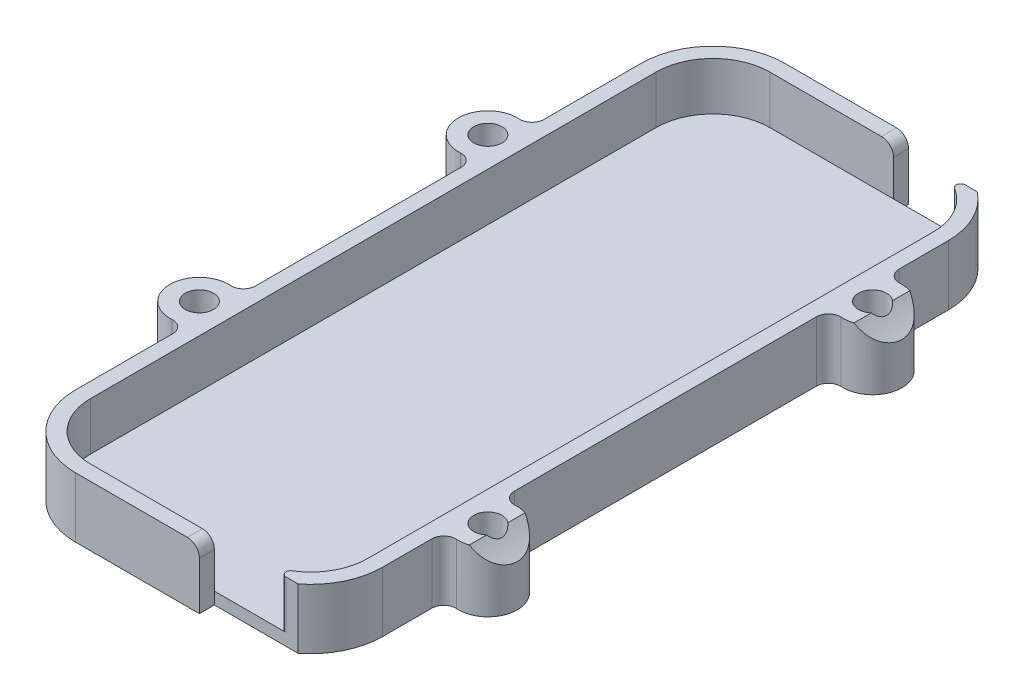
SolidWorks part; units mm, degrees
ref_plane "Front" through (0, 0, 0) normal (0, 0, 1) x (1, 0, 0)
ref_plane "Top" through (0, 0, 0) normal (0, 1, 0) x (1, 0, 0)
ref_plane "Right" through (0, 0, 0) normal (1, 0, 0) x (0, 0, -1)
ref_axis "side-side" through (80.9, 0, 0) along (-1, 0, 0)
ref_axis "up-down" through (0, 50, 0) along (0, -1, 0)
ref_axis "front-back" through (0, 0, -80.9) along (0, 0, 1)
sketch3d "3DSketch1"
  line L3 (-84.85, 48.65, 7.675) -> (-89, 48.65, 7.675)
  line L8 (-80.0996, 87.5542, 66.8971) -> (-111.9004, 87.5542, 66.8971)
  line L9 (-111.9004, 87.5542, 66.8971) -> (-111.9004, 87.5542, 49.7013)
  line L10 (-111.9004, 87.5542, 49.7013) -> (-80.0996, 87.5542, 49.7013)
  line L11 (-80.0996, 87.5542, 49.7013) -> (-80.0996, 87.5542, 66.8971)
  line L16 (-109.9954, 87.5542, 52) -> (-109.9954, 87.5542, 64.5984)
  line L17 (-109.9954, 87.5542, 64.5984) -> (-82.0046, 87.5542, 64.5984)
  line L18 (-82.0046, 87.5542, 64.5984) -> (-82.0046, 87.5542, 52)
  line L19 (-82.0046, 87.5542, 52) -> (-109.9954, 87.5542, 52)
  line L24 (-72, 34.65, 48) -> (-168, 34.65, 48)
  line L25 (-168, 34.65, 48) -> (-168, 62.65, 48)
  line L26 (-166, 64.65, 48) -> (-74, 64.65, 48)
  line L27 (-72, 62.65, 48) -> (-72, 34.65, 48)
  line L32 (-22.2, 34.65, -47.05) -> (-22.2, 34.65, 47.05)
  line L33 (-30.4, 34.65, 55.25) -> (-57.6, 34.65, 55.25)
  line L34 (-65.8, 34.65, 47.05) -> (-65.8, 34.65, -47.05)
  line L35 (-57.6, 34.65, -55.25) -> (-30.4, 34.65, -55.25)
  line L40 (-21.2, 35.65, 47.05) -> (-21.2, 35.65, -47.05)
  line L41 (-30.4, 35.65, -56.25) -> (-57.6, 35.65, -56.25)
  line L42 (-66.8, 35.65, -47.05) -> (-66.8, 35.65, 47.05)
  line L43 (-57.6, 35.65, 56.25) -> (-30.4, 35.65, 56.25)
  line L56 (-18.5394, 56.65, 57.65) -> (-36, 56.65, 57.65)
  line L57 (-36, 56.65, 57.65) -> (-36, 59.85, 57.65)
  line L58 (-34.5, 61.35, 57.65) -> (-24.4367, 61.35, 57.65)
  line L59 (26.2059, 54.95, 57.65) -> (34.5, 54.95, 57.65)
  line L60 (36, 53.45, 57.65) -> (36, 32.65, 57.65)
  line L61 (36, 32.65, 57.65) -> (-36, 32.65, 57.65)
  line L62 (-36, 32.65, 57.65) -> (-36, 53.65, 57.65)
  line L63 (-36, 53.65, 57.65) -> (-18.5394, 53.65, 57.65)
  line L64 (-96, 52.65, 40) -> (-96, 116.65, 40)
  line L65 (-96, 48.65, -44) -> (-96, 48.65, 36)
  line L66 (-96, 116.65, -48) -> (-96, 52.65, -48)
  line L67 (-96, 120.65, 36) -> (-96, 120.65, -44)
  line L80 (-24.4367, 61.35, -57.65) -> (-34.5, 61.35, -57.65)
  line L81 (-36, 59.85, -57.65) -> (-36, 56.65, -57.65)
  line L82 (-36, 56.65, -57.65) -> (-18.5394, 56.65, -57.65)
  line L83 (-18.5394, 53.65, -57.65) -> (-36, 53.65, -57.65)
  line L84 (-36, 53.65, -57.65) -> (-36, 32.65, -57.65)
  line L85 (-36, 32.65, -57.65) -> (36, 32.65, -57.65)
  line L86 (36, 32.65, -57.65) -> (36, 53.45, -57.65)
  line L87 (34.5, 54.95, -57.65) -> (26.2059, 54.95, -57.65)
  line L88 (-72, 34.65, -48) -> (-72, 62.65, -48)
  line L89 (-74, 64.65, -48) -> (-166, 64.65, -48)
  line L90 (-168, 62.65, -48) -> (-168, 34.65, -48)
  line L91 (-168, 34.65, -48) -> (-72, 34.65, -48)
  line L96 (-150, 32.65, -16) -> (38, 32.65, -16)
  line L97 (-152, 32.65, -78) -> (-152, 32.65, -18)
  line L98 (38, 32.65, -80) -> (-150, 32.65, -80)
  line L99 (40, 32.65, -18) -> (40, 32.65, -78)
  line L104 (-150, 32.65, 80) -> (38, 32.65, 80)
  line L105 (40, 32.65, 78) -> (40, 32.65, 18)
  line L106 (38, 32.65, 16) -> (-150, 32.65, 16)
  line L107 (-152, 32.65, 18) -> (-152, 32.65, 78)
  line L108 (-84.85, 48.65, 16.325) -> (-84.85, 48.65, 7.675)
  line L109 (-89, 48.65, 16.325) -> (-84.85, 48.65, 16.325)
  arc A4 (-168, 62.65, 48) -> (-166, 64.65, 48) centre (-166, 62.65, 48) ccw
  arc A5 (-74, 64.65, 48) -> (-72, 62.65, 48) centre (-74, 62.65, 48) ccw
  circle A6 centre (0, 55.15, 15.5) radius 17.6
  arc A12 (-22.2, 34.65, 47.05) -> (-30.4, 34.65, 55.25) centre (-30.4, 34.65, 47.05) ccw
  arc A13 (-57.6, 34.65, 55.25) -> (-65.8, 34.65, 47.05) centre (-57.6, 34.65, 47.05) ccw
  arc A14 (-65.8, 34.65, -47.05) -> (-57.6, 34.65, -55.25) centre (-57.6, 34.65, -47.05) ccw
  arc A15 (-30.4, 34.65, -55.25) -> (-22.2, 34.65, -47.05) centre (-30.4, 34.65, -47.05) ccw
  circle A16 centre (-96, 52.65, -44) radius 2.1
  arc A22 (-21.2, 35.65, -47.05) -> (-30.4, 35.65, -56.25) centre (-30.4, 35.65, -47.05) ccw
  arc A23 (-57.6, 35.65, -56.25) -> (-66.8, 35.65, -47.05) centre (-57.6, 35.65, -47.05) ccw
  arc A24 (-66.8, 35.65, 47.05) -> (-57.6, 35.65, 56.25) centre (-57.6, 35.65, 47.05) ccw
  arc A25 (-30.4, 35.65, 56.25) -> (-21.2, 35.65, 47.05) centre (-30.4, 35.65, 47.05) ccw
  circle A26 centre (-96, 84.65, -44) radius 2.1
  circle A28 centre (-96, 84.65, 36) radius 2.1
  arc A36 (-36, 59.85, 57.65) -> (-34.5, 61.35, 57.65) centre (-34.5, 59.85, 57.65) ccw
  arc A37 (-24.4367, 61.35, 57.65) -> (-20.7453, 63.8092, 57.65) centre (-24.4367, 65.35, 57.65) ccw
  arc A38 (-20.7453, 63.8092, 57.65) -> (22.2473, 58.376, 57.65) centre (0, 55.15, 57.65) ccw
  arc A39 (22.2473, 58.376, 57.65) -> (26.2059, 54.95, 57.65) centre (26.2059, 58.95, 57.65) ccw
  arc A40 (34.5, 54.95, 57.65) -> (36, 53.45, 57.65) centre (34.5, 53.45, 57.65) ccw
  arc A41 (-18.5394, 53.65, 57.65) -> (-18.5394, 56.65, 57.65) centre (0, 55.15, 57.65) ccw
  arc A46 (-96, 48.65, 36) -> (-96, 52.65, 40) centre (-96, 52.65, 36) ccw
  arc A47 (-96, 52.65, -48) -> (-96, 48.65, -44) centre (-96, 52.65, -44) ccw
  arc A48 (-96, 120.65, -44) -> (-96, 116.65, -48) centre (-96, 116.65, -44) ccw
  arc A49 (-96, 116.65, 40) -> (-96, 120.65, 36) centre (-96, 116.65, 36) ccw
  circle A50 centre (-96, 68.65, 36) radius 2.1
  circle A52 centre (-96, 52.65, 36) radius 2.1
  circle A54 centre (-96, 68.65, -44) radius 2.1
  arc A58 (-72, 62.65, -48) -> (-74, 64.65, -48) centre (-74, 62.65, -48) ccw
  arc A59 (-166, 64.65, -48) -> (-168, 62.65, -48) centre (-166, 62.65, -48) ccw
  arc A66 (26.2059, 54.95, -57.65) -> (22.2473, 58.376, -57.65) centre (26.2059, 58.95, -57.65) ccw
  arc A67 (22.2473, 58.376, -57.65) -> (-20.7453, 63.8092, -57.65) centre (0, 55.15, -57.65) ccw
  arc A68 (-20.7453, 63.8092, -57.65) -> (-24.4367, 61.35, -57.65) centre (-24.4367, 65.35, -57.65) ccw
  arc A69 (-34.5, 61.35, -57.65) -> (-36, 59.85, -57.65) centre (-34.5, 59.85, -57.65) ccw
  arc A70 (-18.5394, 56.65, -57.65) -> (-18.5394, 53.65, -57.65) centre (0, 55.15, -57.65) ccw
  arc A71 (36, 53.45, -57.65) -> (34.5, 54.95, -57.65) centre (34.5, 53.45, -57.65) ccw
  arc A78 (-152, 32.65, -18) -> (-150, 32.65, -16) centre (-150, 32.65, -18) ccw
  arc A79 (-150, 32.65, -80) -> (-152, 32.65, -78) centre (-150, 32.65, -78) ccw
  arc A80 (40, 32.65, -78) -> (38, 32.65, -80) centre (38, 32.65, -78) ccw
  arc A81 (38, 32.65, -16) -> (40, 32.65, -18) centre (38, 32.65, -18) ccw
  arc A86 (38, 32.65, 80) -> (40, 32.65, 78) centre (38, 32.65, 78) ccw
  arc A87 (40, 32.65, 18) -> (38, 32.65, 16) centre (38, 32.65, 18) ccw
  arc A88 (-150, 32.65, 16) -> (-152, 32.65, 18) centre (-150, 32.65, 18) ccw
  arc A89 (-152, 32.65, 78) -> (-150, 32.65, 80) centre (-150, 32.65, 78) ccw
  arc A119 (-130.34, 32.65, 28.19) -> (-130.34, 32.65, 24.49) centre (-130.34, 32.65, 26.34) ccw
  arc A120 (-130.34, 32.65, -35.81) -> (-130.34, 32.65, -39.51) centre (-130.34, 32.65, -37.66) ccw
  arc A121 (-136, 32.65, -38.15) -> (-136, 32.65, -41.85) centre (-136, 32.65, -40) ccw
  arc A122 (-72, 32.65, 25.85) -> (-72, 32.65, 22.15) centre (-72, 32.65, 24) ccw
  arc A123 (-80, 32.65, 33.85) -> (-80, 32.65, 30.15) centre (-80, 32.65, 32) ccw
  arc A124 (-109.66, 32.65, 28.19) -> (-109.66, 32.65, 24.49) centre (-109.66, 32.65, 26.34) ccw
  arc A125 (-112, 32.65, 33.85) -> (-112, 32.65, 30.15) centre (-112, 32.65, 32) ccw
  arc A126 (-72, 32.65, 41.85) -> (-72, 32.65, 38.15) centre (-72, 32.65, 40) ccw
  arc A127 (-72, 32.65, 36) -> (-72, 32.65, 28) centre (-72, 32.65, 32) ccw
  arc A128 (-13.66, 30.65, 24.49) -> (-13.66, 30.65, 28.19) centre (-13.66, 30.65, 26.34) ccw
  arc A129 (-16, 30.65, 30.15) -> (-16, 30.65, 33.85) centre (-16, 30.65, 32) ccw
  arc A130 (-8, 30.65, 38.15) -> (-8, 30.65, 41.85) centre (-8, 30.65, 40) ccw
  arc A131 (-13.66, 30.65, -28.19) -> (-13.66, 30.65, -24.49) centre (-13.66, 30.65, -26.34) ccw
  arc A132 (-8, 30.65, -25.85) -> (-8, 30.65, -22.15) centre (-8, 30.65, -24) ccw
  arc A133 (-16, 30.65, -33.85) -> (-16, 30.65, -30.15) centre (-16, 30.65, -32) ccw
  arc A134 (-13.66, 30.65, -60.19) -> (-13.66, 30.65, -56.49) centre (-13.66, 30.65, -58.34) ccw
  arc A135 (-8, 30.65, -41.85) -> (-8, 30.65, -38.15) centre (-8, 30.65, -40) ccw
  arc A136 (-13.66, 30.65, -39.51) -> (-13.66, 30.65, -35.81) centre (-13.66, 30.65, -37.66) ccw
  arc A137 (-136, 32.65, 36) -> (-136, 32.65, 28) centre (-136, 32.65, 32) ccw
  arc A138 (-128, 32.65, 33.85) -> (-128, 32.65, 30.15) centre (-128, 32.65, 32) ccw
  arc A139 (-104, 32.65, 41.85) -> (-104, 32.65, 38.15) centre (-104, 32.65, 40) ccw
  arc A140 (-104, 32.65, 25.85) -> (-104, 32.65, 22.15) centre (-104, 32.65, 24) ccw
  arc A141 (-104, 32.65, 36) -> (-104, 32.65, 28) centre (-104, 32.65, 32) ccw
  arc A142 (-136, 32.65, 25.85) -> (-136, 32.65, 22.15) centre (-136, 32.65, 24) ccw
  arc A143 (-128, 32.65, -30.15) -> (-128, 32.65, -33.85) centre (-128, 32.65, -32) ccw
  arc A144 (-136, 32.65, -22.15) -> (-136, 32.65, -25.85) centre (-136, 32.65, -24) ccw
  arc A145 (-144, 32.65, -30.15) -> (-144, 32.65, -33.85) centre (-144, 32.65, -32) ccw
  arc A146 (-136, 32.65, -28) -> (-136, 32.65, -36) centre (-136, 32.65, -32) ccw
  arc A147 (-104, 32.65, -28) -> (-104, 32.65, -36) centre (-104, 32.65, -32) ccw
  arc A148 (-112, 32.65, -30.15) -> (-112, 32.65, -33.85) centre (-112, 32.65, -32) ccw
  arc A149 (-98.34, 32.65, -35.81) -> (-98.34, 32.65, -39.51) centre (-98.34, 32.65, -37.66) ccw
  arc A150 (-109.66, 32.65, -24.49) -> (-109.66, 32.65, -28.19) centre (-109.66, 32.65, -26.34) ccw
  arc A151 (-104, 32.65, -25.85) -> (-104, 32.65, -22.15) centre (-104, 32.65, -24) ccw
  point P22 (-166, 62.65, 46)
  point P23 (-74, 62.65, 46)
  point P43 (0, 55.15, 33.1)
  point P44 (-30.4, 26.45, 47.05)
  point P45 (-57.6, 26.45, 47.05)
  point P46 (-57.6, 26.45, -47.05)
  point P47 (-30.4, 26.45, -47.05)
  point P68 (-93.9, 52.65, -44)
  point P69 (-30.4, 44.85, -47.05)
  point P70 (-57.6, 44.85, -47.05)
  point P71 (-57.6, 44.85, 47.05)
  point P72 (-30.4, 44.85, 47.05)
  point P91 (-93.9, 84.65, -44)
  point P107 (-34.5, 59.85, 56.15)
  point P108 (-24.4367, 65.35, 61.65)
  point P110 (0, 55.15, 35.17)
  point P111 (26.2059, 58.95, 61.65)
  point P112 (34.5, 53.45, 56.15)
  point P113 (0, 55.15, 76.25)
  point P130 (-93.9, 84.65, 36)
  point P131 (-100, 52.65, 36)
  point P132 (-100, 52.65, -44)
  point P133 (-100, 116.65, -44)
  point P134 (-100, 116.65, 36)
  point P139 (-93.9, 68.65, 36)
  point P144 (-93.9, 52.65, 36)
  point P149 (-93.9, 68.65, -44)
  point P185 (26.2059, 58.95, -61.65)
  point P186 (0, 55.15, -35.17)
  point P187 (-24.4367, 65.35, -61.65)
  point P188 (-34.5, 59.85, -56.15)
  point P189 (0, 55.15, -76.25)
  point P190 (34.5, 53.45, -56.15)
  point P193 (-74, 62.65, -46)
  point P194 (-166, 62.65, -46)
  point P215 (-150, 34.65, -18)
  point P216 (-150, 34.65, -78)
  point P217 (38, 34.65, -78)
  point P218 (38, 34.65, -18)
  point P235 (38, 34.65, 78)
  point P236 (38, 34.65, 18)
  point P237 (-150, 34.65, 18)
  point P238 (-150, 34.65, 78)
  point P306 (-130.34, 34.5, 26.34)
  point P308 (-130.34, 34.5, -37.66)
  point P369 (-136, 34.5, -40)
  point P370 (-72, 34.5, 24)
  point P371 (-80, 34.5, 32)
  point P372 (-109.66, 34.5, 26.34)
  point P373 (-112, 34.5, 32)
  point P374 (-72, 34.5, 40)
  point P375 (-72, 36.65, 32)
  point P376 (-13.66, 32.5, 26.34)
  point P377 (-16, 32.5, 32)
  point P378 (-8, 32.5, 40)
  point P379 (-13.66, 32.5, -26.34)
  point P380 (-8, 32.5, -24)
  point P381 (-16, 32.5, -32)
  point P382 (-13.66, 32.5, -58.34)
  point P383 (-8, 32.5, -40)
  point P384 (-13.66, 32.5, -37.66)
  point P385 (-136, 36.65, 32)
  point P386 (-128, 34.5, 32)
  point P387 (-104, 34.5, 40)
  point P388 (-104, 34.5, 24)
  point P389 (-104, 36.65, 32)
  point P390 (-136, 34.5, 24)
  point P391 (-128, 34.5, -32)
  point P392 (-136, 34.5, -24)
  point P393 (-144, 34.5, -32)
  point P394 (-136, 36.65, -32)
  point P395 (-104, 36.65, -32)
  point P396 (-112, 34.5, -32)
  point P397 (-98.34, 34.5, -37.66)
  point P398 (-109.66, 34.5, -26.34)
  point P399 (-104, 34.5, -24)
ref_plane "Plane1" through (0, 32.65, 0) normal (0, 1, 0) x (1, 0, 0)
sketch "Sketch1" plane through (0, 32.65, 0) normal (0, 1, 0) x (1, 0, 0)
  line L8 (-20.95, -47.05) -> (-20.95, 47.05)
  line L9 (-57.6, -56.5) -> (-30.4, -56.5)
  line L10 (-67.05, 47.05) -> (-67.05, -47.05)
  line L11 (-30.4, 56.5) -> (-57.6, 56.5)
  line L12 (-20.95, -47.05) -> (-20.95, 47.05)
  line L13 (-57.6, -56.5) -> (-30.4, -56.5)
  line L14 (-67.05, 47.05) -> (-67.05, -47.05)
  line L15 (-30.4, 56.5) -> (-57.6, 56.5)
  arc A8 (-20.95, 47.05) -> (-30.4, 56.5) centre (-30.4, 47.05) ccw
  arc A9 (-30.4, -56.5) -> (-20.95, -47.05) centre (-30.4, -47.05) ccw
  arc A10 (-67.05, -47.05) -> (-57.6, -56.5) centre (-57.6, -47.05) ccw
  arc A11 (-57.6, 56.5) -> (-67.05, 47.05) centre (-57.6, 47.05) ccw
  arc A12 (-20.95, 47.05) -> (-30.4, 56.5) centre (-30.4, 47.05) ccw
  arc A13 (-30.4, -56.5) -> (-20.95, -47.05) centre (-30.4, -47.05) ccw
  arc A14 (-67.05, -47.05) -> (-57.6, -56.5) centre (-57.6, -47.05) ccw
  arc A15 (-57.6, 56.5) -> (-67.05, 47.05) centre (-57.6, 47.05) ccw
  dimension "D1" = 0.25
extrude "Extrude-Thin1" add sketch "Sketch1" along normal blind 10 thin thin type one direction wall 2.5
extrude "Boss-Extrude1" add sketch "Sketch1<2>" along normal blind 2
sketch "Sketch1<2>" plane through (0, 32.65, 0) normal (0, 1, 0) x (1, 0, 0) same geometry as "Sketch1"
sketch "Sketch2" plane through (0, 42.65, 0) normal (0, 1, 0) x (1, 0, 0)
  line L0 (-30.4, 56.5) -> (-57.6, 56.5) construction
  line L1 (-37, 63.7647) -> (-11.1659, 63.7647)
  line L2 (-37, 63.7647) -> (-37, 56.5)
  line L3 (-37, 56.5) -> (-11.1659, 56.5)
  line L4 (-11.1659, 63.7647) -> (-11.1659, 56.5)
  line L5 (-57.6, -56.5) -> (-30.4, -56.5) construction
  line L6 (-37, -56.5) -> (-10.2928, -56.5)
  line L7 (-37, -56.5) -> (-37, -62.7441)
  line L8 (-37, -62.7441) -> (-10.2928, -62.7441)
  line L9 (-10.2928, -56.5) -> (-10.2928, -62.7441)
  dimension "D1" = 1
extrude "Cut-Extrude1" cut sketch "Sketch2" against normal through all
sketch "Sketch3" plane through (0, 42.65, 0) normal (0, 1, 0) x (1, 0, 0)
  line L0 (0, 0) -> (-90.8587, 0) construction
  circle A0 centre (-72, -24) radius 4.9
  circle A1 centre (-16, -32) radius 4.9
  circle A2 centre (-16, 32) radius 4.9
  circle A3 centre (-72, 24) radius 4.9
  dimension "D1" = 9.8
extrude "Boss-Extrude2" add sketch "Sketch3" against normal up to surface (10 mm away) up to face at (-40.6773, 32.65, 0)
fillet "Fillet1" radius 0.75 2 edges at (-30.4, 38.65, -56.5) (-30.4, 38.65, 56.5)
fillet "Fillet2" radius 2 10 edges at (-37, 42.65, 57.75) (-37, 42.65, -57.75) (-18.45, 37.65, 36.2435) (-18.45, 37.65, 27.7565) (-18.45, 37.65, -27.7565) (-18.45, 37.65, -36.2435) (-69.55, 37.65, 19.7565) (-69.55, 37.65, -28.2435) (-69.55, 37.65, 28.2435) (-69.55, 37.65, -19.7565)
sketch "Sketch5" plane through (0, 0, 0) normal (0, 0, 1) x (1, 0, 0)
  circle A0 centre (0, 55.15) radius 19.1
  circle A1 centre (0, 55.15) radius 17.6 construction
  dimension "D1" = 1.5
extrude "Cut-Extrude2" cut sketch "Sketch5" against normal through all both and the other way through all
sketch "Sketch6" plane through (0, 32.65, 0) normal (0, -1, 0) x (1, 0, 0)
  circle A0 centre (-72, 24) radius 2.6162
  circle A2 centre (-16, 32) radius 2.6162
  circle A3 centre (-16, -32) radius 2.6162
  circle A4 centre (-72, -24) radius 2.6162
  dimension "D1" = 5.2324
extrude "Cut-Extrude3" cut sketch "Sketch6" against normal blind 5 draft 8
sketch "Sketch7" plane through (0, 32.65, 0) normal (0, -1, 0) x (1, 0, 0)
  circle A0 centre (-72, 24) radius 2.3495
  circle A1 centre (-16, 32) radius 2.3495
  circle A2 centre (-16, -32) radius 2.3495
  circle A3 centre (-72, -24) radius 2.3495
  dimension "D1" = 4.699
extrude "Cut-Extrude4" cut sketch "Sketch7" against normal through all
